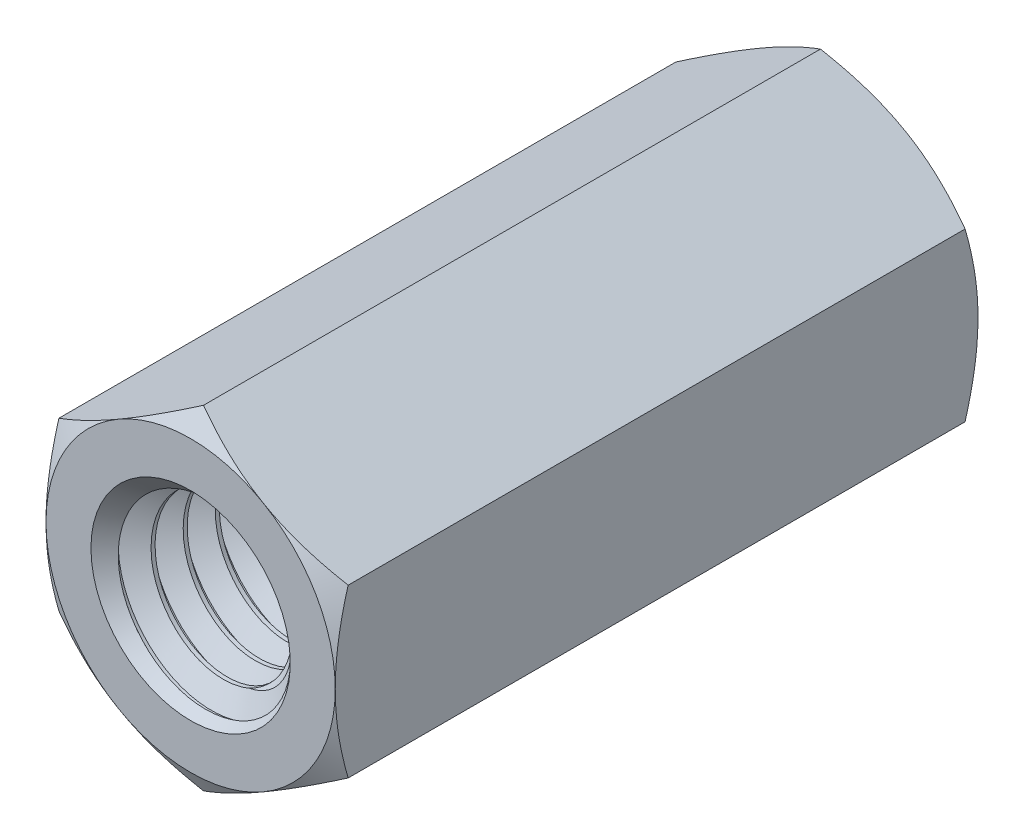
SolidWorks part; units mm, degrees
ref_plane "Front Plane" through (0, 0, 0) normal (0, 0, 1) x (1, 0, 0)
ref_plane "Top Plane" through (0, 0, 0) normal (0, 1, 0) x (1, 0, 0)
ref_plane "Right Plane" through (0, 0, 0) normal (1, 0, 0) x (0, 0, -1)
sketch "Sketch3" plane through (0, 0, 0) normal (1, 0, 0) x (0, 0, -1)
  line L0 (-5, 0) -> (5, 0) construction
  line L1 (0, 2.25) -> (0, -2.25) construction
  line L2 (-5, 1.5) -> (-5, -1.5) construction
  point P2 (-1.3, 0)
  point P3 (1.3, 0)
  dimension "D1" = 6.3
  dimension "Length" = 10
  dimension "Min Thread Length" = 6.3
  dimension "Thread Dia" = 3
  dimension "Hex" = 4.5
sketch "Sketch1" plane through (0, 0, 0) normal (0, 0, 1) x (1, 0, 0)
  line L1 (0, 2.5981) -> (-2.25, 1.299)
  line L2 (-2.25, 1.299) -> (-2.25, -1.299)
  line L3 (-2.25, -1.299) -> (0, -2.5981)
  line L4 (0, -2.5981) -> (2.25, -1.299)
  line L5 (2.25, -1.299) -> (2.25, 1.299)
  line L6 (2.25, 1.299) -> (0, 2.5981)
  circle A0 centre (0, 0) radius 2.25 construction
  circle A1 centre (0, 0) radius 1.5
extrude "Extrude1" add sketch "Sketch1" along normal up to vertex (5 mm away) and the other way up to vertex (5 mm away) up to point (0, 0, 5) other way up to point (0, 0, -5)
sketch "Sketch11" plane through (0, 0, -5) normal (0, 0, -1) x (-1, 0, 0)
  circle A0 centre (0, 0) radius 1.5 construction
  circle A1 centre (0, 0) radius 1.5
curve "Helix/Spiral1" pitch 0.5 height 10.5 radius 1.5 centre (0, 0, -5) axis (0, 0, 1) start towards (0, 1, 0) parameters "Pitch"=0.5
sketch "Sketch12" plane through (0, 0, 0) normal (1, 0, 0) x (0, 0, -1)
  line L0 (5.4375, 1.5) -> (5, 1.5)
  line L1 (5.4375, 1.5) -> (5.25, 1.1752)
  line L2 (5.25, 1.1752) -> (5.1875, 1.1752)
  line L3 (5.1875, 1.1752) -> (5, 1.5)
  line L4 (5.2188, 1.1752) -> (5.2188, 1.5) construction
  line L5 (5.3438, 1.3376) -> (5.0938, 1.3376) construction
  dimension "D1" = 0.0625
  dimension "D2" = 0.25
  dimension "D3" = 60
sweep "Sweep1" add profiles "Sketch12" path "Helix/Spiral1"
sketch "Sketch6" plane through (0, 0, -5) normal (0, 0, -1) x (-1, 0, 0)
  line L6 (0, 2.5981) -> (-2.25, 1.299)
  line L7 (-2.25, 1.299) -> (-2.25, -1.299)
  line L8 (-2.25, -1.299) -> (0, -2.5981)
  line L9 (0, -2.5981) -> (2.25, -1.299)
  line L10 (2.25, -1.299) -> (2.25, 1.299)
  line L11 (2.25, 1.299) -> (0, 2.5981)
  line L12 (0, 2.5981) -> (-2.25, 1.299)
  line L13 (-2.25, 1.299) -> (-2.25, -1.299)
  line L14 (-2.25, -1.299) -> (0, -2.5981)
  line L15 (0, -2.5981) -> (2.25, -1.299)
  line L16 (2.25, -1.299) -> (2.25, 1.299)
  line L17 (2.25, 1.299) -> (0, 2.5981)
  dimension "D1" = 0
extrude "Extrude2" cut sketch "Sketch6" along normal through all
sketch "Sketch7" plane through (0, 0, -5) normal (0, 0, -1) x (-1, 0, 0)
  circle A2 centre (0, 0) radius 1.5508
  circle A3 centre (0, 0) radius 1.5508
  dimension "D1" = 0.0508
extrude "Extrude3" cut sketch "Sketch7" against normal through all draft 43
sketch "Sketch8" plane through (0, 0, -5) normal (0, 0, -1) x (-1, 0, 0)
  circle A0 centre (0, 0) radius 2.25 construction
  circle A1 centre (0, 0) radius 2.25
extrude "Extrude4" cut sketch "Sketch8" against normal through all draft 60 flip side to cut
mirror "Mirror1" about plane through (0, 0, 0) normal (0, 0, 1) of "Extrude2", "Extrude3", "Extrude4"
sketch "Sketch9" [suppressed] plane through (0, 0, 0) normal (1, 0, 0) x (0, 0, -1)
  line L1 (-3.7, 1.5508) -> (3.7, 1.5508)
  line L2 (-3.7, 1.5508) -> (-3.7, 0)
  line L3 (-3.7, 0) -> (3.7, 0)
  line L4 (3.7, 1.5508) -> (3.7, 0)
  line L7 (-10, 0) -> (10, 0) construction
revolve "Revolve" [suppressed] add sketch "Sketch9" angle 360 about L0
sketch "Sketch10" plane through (0, 0, 0) normal (1, 0, 0) x (0, 0, -1)
  line L0 (5, 1.5) -> (-1.3, 1.5)
  line L1 (-5, 1.5) -> (1.3, 1.5)
  line L2 (-1.3, 1.5) -> (-1.3, -1.5)
  line L3 (-5, -1.5508) -> (1.3, -1.5508)
  line L4 (1.3, 1.5) -> (1.3, -1.5508)
  line L5 (-1.3, -1.5) -> (5, -1.5)
equation "\"D1@Sketch3\" = \"Min Thread Length@Sketch3\""
equation "\"D3@Helix/Spiral1\" = \"Length@Sketch3\"+\"Pitch@Helix/Spiral1\""
equation "\"D1@Sketch12\" = \"Pitch@Helix/Spiral1\"*.125"
equation "\"D2@Sketch12\" = \"Pitch@Helix/Spiral1\"*.5"
